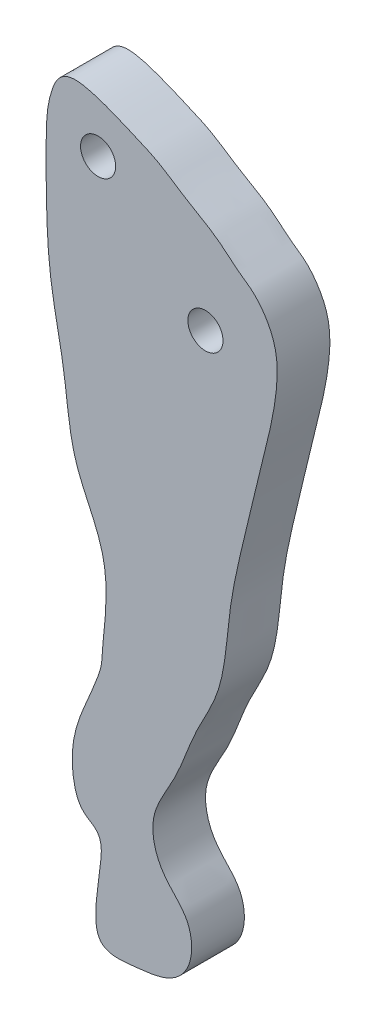
SolidWorks part; units mm, degrees
ref_plane "Спереди" through (0, 0, 0) normal (0, 0, 1) x (1, 0, 0)
ref_plane "Сверху" through (0, 0, 0) normal (0, 1, 0) x (1, 0, 0)
ref_plane "Справа" through (0, 0, 0) normal (1, 0, 0) x (0, 0, -1)
other "Configuration Table"
sketch "Sketch1" plane through (0, 0, 0) normal (0, 0, 1) x (1, 0, 0)
  circle A0 centre (-6.7616, 4.1218) radius 1
  circle A1 centre (-12.8747, 9.6623) radius 1
  spline S0 degree 3 poles (-15.8441, 9.5264) (-15.7245, 11.3822) (-14.6943, 13.3755) (-10.7472, 11.6856) (-9.3789, 11.1011) (-7.9356, 10.0667) (-6.0862, 9.0767) (-5.2241, 8.2406) (-4.4681, 7.6881) (-3.8196, 7.2649) (-2.6509, 5.6577) (-2.6299, 3.302) (-3.1021, 0.9077) (-3.6994, -1.3468) (-4.4707, -4.7299) (-5.5278, -8.8478) (-5.6314, -13.0445) (-7.5078, -16.094) (-8.3489, -18.8594) (-10.0992, -21.2773) (-9.4077, -23.9484) (-7.568, -25.2776) (-7.4213, -27.7007) (-8.6939, -29.0444) (-11.0194, -29.2758) (-13.2741, -29.5418) (-12.747, -24.9861) (-12.4487, -23.6774) (-14.1267, -22.9906) (-14.5673, -19.9678) (-12.4673, -15.1429) (-12.8446, -15.7321) (-12.0345, -9.8014) (-14.4535, -6.3482) (-14.6831, -1.986) (-15.7086, 2.2192) (-15.8378, 5.9902) (-15.8441, 9.5264) (-15.7245, 11.3822) (-14.6943, 13.3755) knots -0.107085 -0.057315 -0.028029 0 0.019168 0.035852 0.049221 0.065363 0.080616 0.094734 0.09682 0.101479 0.125428 0.150735 0.177783 0.196742 0.232864 0.285139 0.334734 0.362744 0.397642 0.427729 0.452921 0.476299 0.496976 0.520565 0.535628 0.556474 0.575337 0.609705 0.622666 0.634741 0.653971 0.715132 0.757144 0.80452 0.849469 0.892915 0.942685 0.971971 1 1.019168 1.035852 1.049221 only from (-15.4682, 11.7127) to (-15.4682, 11.7127)
  point P6 (-13.7895, 12.9659)
  point P8 (-15.4682, 11.7127)
  point P10 (-13.9977, 12.7814)
  dimension "D2" = 2
extrude "Boss-Extrude1" add sketch "Sketch1" along normal blind 3
equation "\"R small\"= 2"
equation "\"R big\"= 4"
equation "\"width\"= 0.6"
equation "\"border width\"= 1"
equation "\"D2@Sketch1\"=\"R small\""
